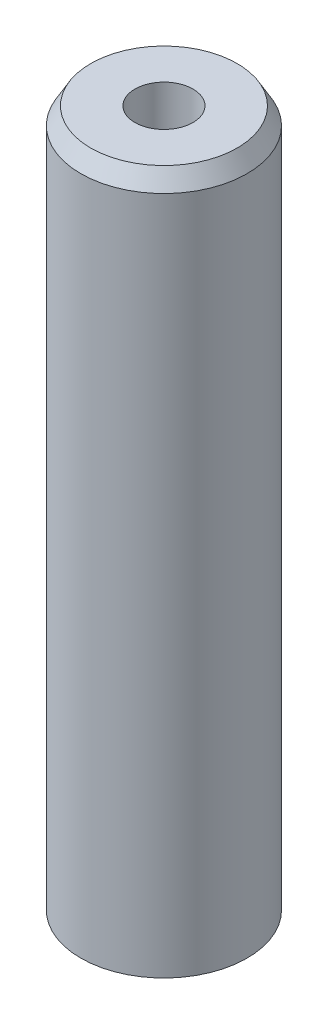
SolidWorks part; units mm, degrees
ref_plane "Front Plane" through (0, 0, 0) normal (0, 0, 1) x (1, 0, 0)
ref_plane "Top Plane" through (0, 0, 0) normal (0, 1, 0) x (1, 0, 0)
ref_plane "Right Plane" through (0, 0, 0) normal (1, 0, 0) x (0, 0, -1)
sketch "Sketch1" plane through (0, 0, 0) normal (0, 1, 0) x (1, 0, 0)
  circle A0 centre (0, 0) radius 25
  dimension "SHAFT_OD" = 50
extrude "Boss-Extrude1" add sketch "Sketch1" along normal blind 212.3888
sketch "Sketch2" plane through (0, 0, 0) normal (0, 1, 0) x (1, 0, 0)
  circle A0 centre (0, 0) radius 8.729
  dimension "BORE_D" = 17.4581
extrude "Cut-Extrude1" cut sketch "Sketch2" along normal through all
chamfer "Chamfer1" distance 5.1756 angle 30 2 edges at (0, 212.3888, 25) (0, 0, 25) first distance on face at (0, 212.3888, 25) first distance on face at (0, 0, 8.729)
